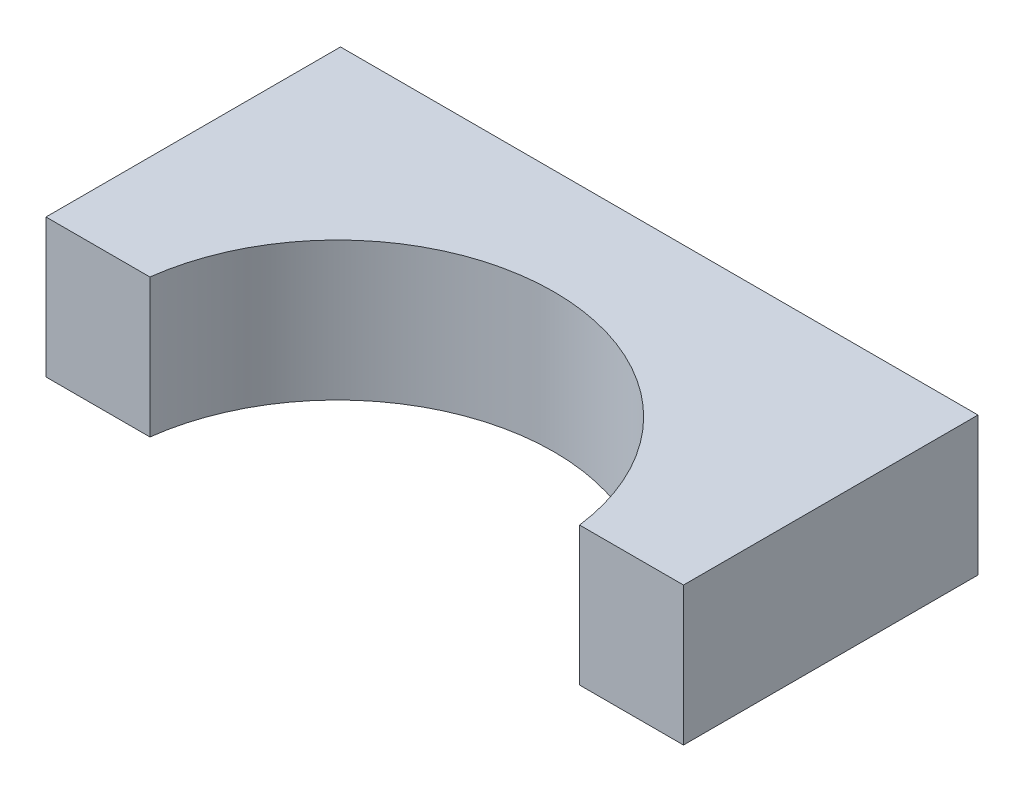
SolidWorks part; units mm, degrees
material "PLA"
ref_plane "Front" through (0, 0, 0) normal (0, 0, 1) x (1, 0, 0)
ref_plane "Top" through (0, 0, 0) normal (0, 1, 0) x (1, 0, 0)
ref_plane "Right" through (0, 0, 0) normal (1, 0, 0) x (0, 0, -1)
sketch "Sketch2" plane through (0, 0, 0) normal (0, 1, 0) x (1, 0, 0)
  line L0 (-14.986, -8.89) -> (-7.366, -8.89)
  line L1 (-14.986, 12.7) -> (31.75, 12.7)
  line L2 (-14.986, 12.7) -> (-14.986, -8.89)
  line L4 (31.75, 12.7) -> (31.75, -8.89)
  line L5 (24.13, -8.89) -> (31.75, -8.89)
  arc A3 (24.13, -8.89) -> (-7.366, -8.89) centre (8.382, -10.894) ccw
  point P0 (0, 0)
  dimension "D5" = 31.75
  dimension "D1" = 46.736
  dimension "D2" = 21.59
  dimension "D3" = 7.62
  dimension "D4" = 7.62
extrude "Boss-Extrude1" add sketch "Sketch2" against normal blind 10.16
